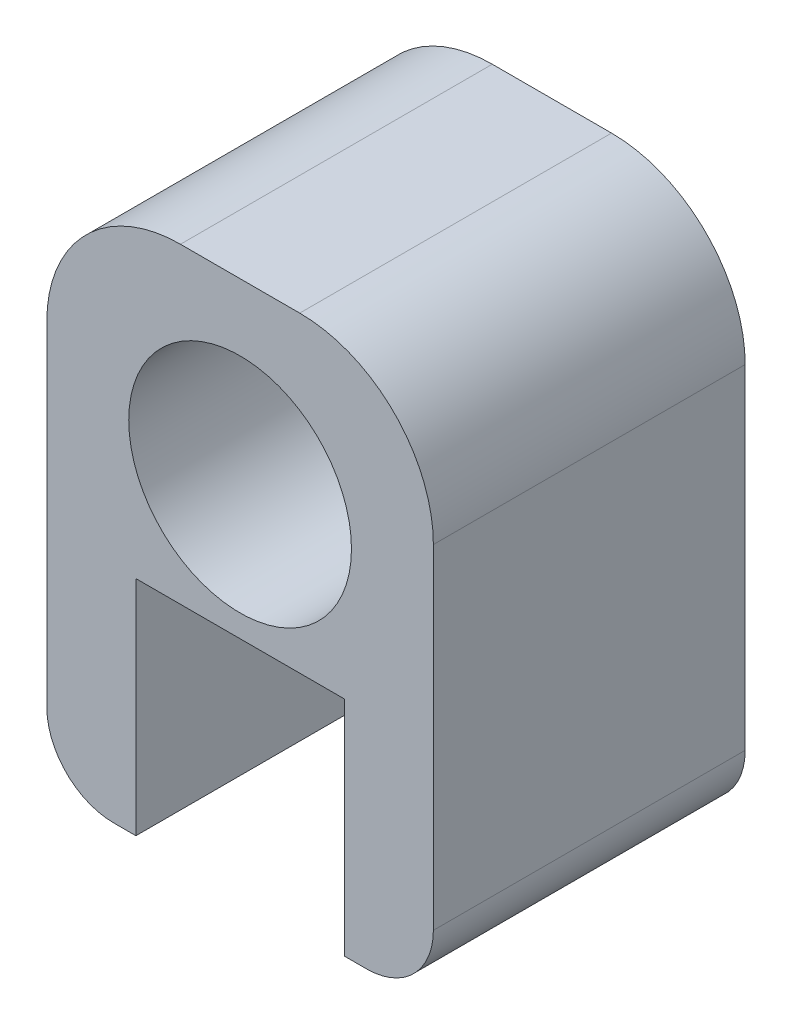
SolidWorks part; units mm, degrees
ref_plane "Front Plane" through (0, 0, 0) normal (0, 0, 1) x (1, 0, 0)
ref_plane "Top Plane" through (0, 0, 0) normal (0, 1, 0) x (1, 0, 0)
ref_plane "Right Plane" through (0, 0, 0) normal (1, 0, 0) x (0, 0, -1)
sketch "Sketch1" plane through (0, 0, 0) normal (0, 0, 1) x (1, 0, 0)
  line L0 (2.3388, 0) -> (-2.3388, 0)
  line L1 (-2.3388, 0) -> (-2.3388, -5)
  line L2 (-2.3388, -5) -> (-4.3388, -5)
  line L3 (-4.3388, -5) -> (-4.3388, 7)
  line L4 (-4.3388, 7) -> (4.3388, 7)
  line L5 (0, 7) -> (0, 0) construction
  line L6 (4.3388, -5) -> (4.3388, 7)
  line L7 (2.3388, -5) -> (4.3388, -5)
  line L8 (2.3388, 0) -> (2.3388, -5)
  dimension "D1" = 2.3388
  dimension "D2" = 2
  dimension "D3" = 7
  dimension "D4" = 5
extrude "Boss-Extrude1" add sketch "Sketch1" against normal blind 7
sketch "Sketch5" plane through (0, 0, 0) normal (0, 0, 1) x (1, 0, 0)
  line L0 (-2.3388, 0) -> (2.3388, 0) construction
  circle A1 centre (0, 3) radius 2.5
  dimension "D1" = 5
  dimension "D2" = 3
extrude "Cut-Extrude2" cut sketch "Sketch5" against normal through all
fillet "Fillet1" radius 3 1 edges at (4.3388, 7, -3.5)
fillet "Fillet2" radius 3 1 edges at (-4.3388, 7, -3.5)
fillet "Fillet3" radius 1.5 1 edges at (4.3388, -5, -3.5)
fillet "Fillet4" radius 1.5 1 edges at (-4.3388, -5, -3.5)
equation "\"LA_width\"=4.67766733"
equation "\"D1@Sketch1\"=\"LA_width\"/2"
equation "\"LA_height\"=6.76462661"
equation "\"LA_length\"=50.00000000"
equation "\"radius_pin\"=2.33883367"
